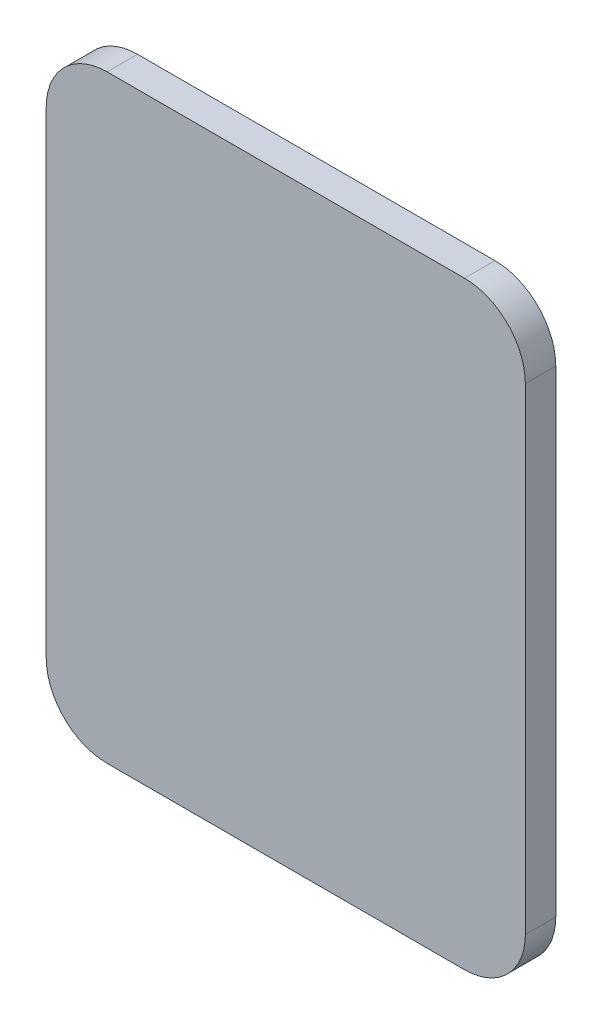
SolidWorks part; units mm, degrees
ref_plane "Front Plane" through (0, 0, 0) normal (0, 0, 1) x (1, 0, 0)
ref_plane "Top Plane" through (0, 0, 0) normal (0, 1, 0) x (1, 0, 0)
ref_plane "Right Plane" through (0, 0, 0) normal (1, 0, 0) x (0, 0, -1)
sketch "Sketch1" plane through (0, 0, 0) normal (0, 0, 1) x (1, 0, 0)
  line L1 (-14.92, -25) -> (14.92, -25)
  line L2 (-20, -19.92) -> (-20, 19.92)
  line L3 (-14.92, 25) -> (14.92, 25)
  line L4 (20, -19.92) -> (20, 19.92)
  line L5 (-20, -25) -> (20, 25) construction
  line L6 (-20, 25) -> (20, -25) construction
  arc A0 (-14.92, -25) -> (-20, -19.92) centre (-14.92, -19.92) cw
  arc A1 (14.92, -25) -> (20, -19.92) centre (14.92, -19.92) ccw
  arc A2 (14.92, 25) -> (20, 19.92) centre (14.92, 19.92) cw
  arc A3 (-20, 19.92) -> (-14.92, 25) centre (-14.92, 19.92) cw
  point P0 (0, 0)
  dimension "D3" = 5.08
  dimension "D1" = 40
  dimension "D2" = 50
extrude "Boss-Extrude1" add sketch "Sketch1" along normal blind 2.54
